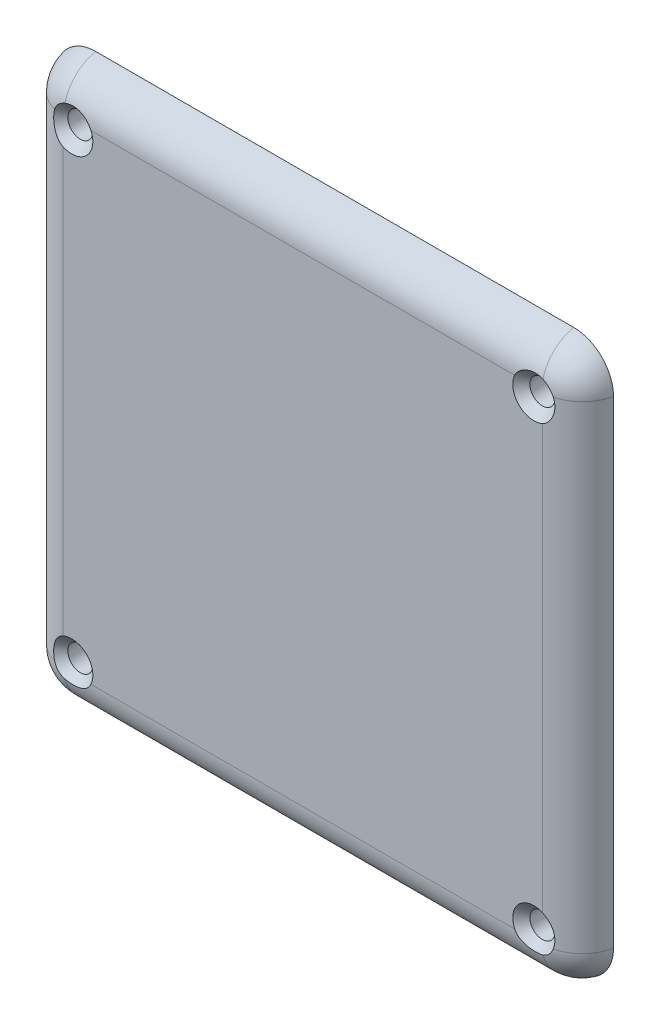
SolidWorks part; units mm, degrees
ref_plane "Front Plane" through (0, 0, 0) normal (0, 0, 1) x (1, 0, 0)
ref_plane "Top Plane" through (0, 0, 0) normal (0, 1, 0) x (1, 0, 0)
ref_plane "Right Plane" through (0, 0, 0) normal (1, 0, 0) x (0, 0, -1)
sketch "Sketch1" plane through (0, 0, 0) normal (0, 0, 1) x (1, 0, 0)
  line L1 (-38.1, -44.45) -> (38.1, -44.45)
  line L2 (-44.45, -38.1) -> (-44.45, 38.1)
  line L3 (-38.1, 44.45) -> (38.1, 44.45)
  line L4 (44.45, -38.1) -> (44.45, 38.1)
  line L5 (-44.45, -44.45) -> (44.45, 44.45) construction
  line L6 (-44.45, 44.45) -> (44.45, -44.45) construction
  arc A0 (38.1, 44.45) -> (44.45, 38.1) centre (38.1, 38.1) cw
  arc A1 (38.1, -44.45) -> (44.45, -38.1) centre (38.1, -38.1) ccw
  arc A2 (-38.1, -44.45) -> (-44.45, -38.1) centre (-38.1, -38.1) cw
  arc A3 (-44.45, 38.1) -> (-38.1, 44.45) centre (-38.1, 38.1) cw
  point P0 (0, 0)
  dimension "D3" = 6.35
  dimension "D1" = 88.9
  dimension "D2" = 88.9
extrude "Boss-Extrude1" add sketch "Sketch1" along normal blind 5.08
fillet "Fillet1" radius 6.35 8 edges at (0, 44.45, 5.08) (42.5901, 42.5901, 5.08) (44.45, 0, 5.08) (42.5901, -42.5901, 5.08) (0, -44.45, 5.08) (-42.5901, -42.5901, 5.08) (-44.45, 0, 5.08) (-42.5901, 42.5901, 5.08)
sketch "Sketch2" plane through (0, 0, 5.08) normal (0, 0, 1) x (1, 0, 0)
  line L0 (-44.45, 38.1) -> (-44.45, -38.1) construction
  line L1 (38.1, 44.45) -> (-38.1, 44.45) construction
  line L3 (-36.83, 36.83) -> (36.83, 36.83) construction
  line L4 (-36.83, 36.83) -> (-36.83, -36.83) construction
  line L5 (-36.83, -36.83) -> (36.83, -36.83) construction
  line L6 (36.83, 36.83) -> (36.83, -36.83) construction
  circle A0 centre (-36.83, 36.83) radius 2.0003
  circle A1 centre (36.83, 36.83) radius 2.0003
  circle A2 centre (36.83, -36.83) radius 2.0003
  circle A3 centre (-36.83, -36.83) radius 2.0003
  dimension "D1" = 4.0005
  dimension "D2" = 4.0005
  dimension "D3" = 4.0005
  dimension "D4" = 4.0005
  dimension "D5" = 7.62
  dimension "D6" = 7.62
  dimension "D7" = 73.66
  dimension "D8" = 73.66
extrude "Cut-Extrude1" cut sketch "Sketch2" against normal up to surface (5.08 mm away) up to face at (0, 0, 0)
sketch "Sketch4" plane through (0, 0, 0) normal (0, 0, -1) x (-1, 0, 0)
  line L0 (-9.779, 9.779) -> (-9.779, 34.925)
  line L1 (-9.779, -34.925) -> (9.779, -34.925)
  line L2 (-9.779, -34.925) -> (-9.779, -9.779)
  line L3 (-9.779, 34.925) -> (9.779, 34.925)
  line L4 (9.779, -34.925) -> (9.779, -9.779)
  line L5 (-9.779, -34.925) -> (9.779, 34.925) construction
  line L6 (-9.779, 34.925) -> (9.779, -34.925) construction
  line L7 (-34.925, -9.779) -> (-9.779, -9.779)
  line L8 (-34.925, -9.779) -> (-34.925, 9.779)
  line L9 (-34.925, 9.779) -> (-9.779, 9.779)
  line L10 (34.925, -9.779) -> (34.925, 9.779)
  line L11 (-34.925, -9.779) -> (34.925, 9.779) construction
  line L12 (-34.925, 9.779) -> (34.925, -9.779) construction
  line L13 (9.779, 9.779) -> (34.925, 9.779)
  line L14 (9.779, 9.779) -> (9.779, 34.925)
  line L15 (9.779, -9.779) -> (34.925, -9.779)
  point P0 (0, 0)
  point P6 (0, 0)
  dimension "D1" = 19.558
  dimension "D2" = 19.558
  dimension "D3" = 69.85
  dimension "D4" = 69.85
extrude "Cut-Extrude2" cut sketch "Sketch4" against normal blind 1.524
hole_wizard "CSK for M3 Hex Socket Countersunk Cap Screw1" positions "Sketch5" profile "Sketch6" countersink size "M3" standard "ISO" end condition through all
sketch "Sketch5" plane through (0, 0, 5.08) normal (0, 0, 1) x (1, 0, 0)
  point P0 (-36.83, 36.83)
  point P3 (36.83, 36.83)
  point P6 (36.83, -36.83)
  point P9 (-36.83, -36.83)
sketch "Sketch6" plane through (-36.83, 36.83, 5.08) normal (1, 0, 0) x (0, -1, 0)
  line L0 (0, 0) -> (0, 5.08)
  line L1 (0, 5.08) -> (1.7, 5.08)
  line L2 (1.7, 5.08) -> (1.7, 1.66)
  line L3 (1.7, 1.66) -> (3.36, 0)
  line L5 (3.36, 0) -> (0, 0)
  line L6 (-1.7, 1.66) -> (-3.36, 0) construction
  line L11 (0, -6.35) -> (0, 107.95) construction
  dimension "Thru Hole Dia." = 3.4
  dimension "Thru Hole Depth" = 5.08
  dimension "Near C'Sink Dia." = 6.72
  dimension "Near C'Sink Angle" = 90
